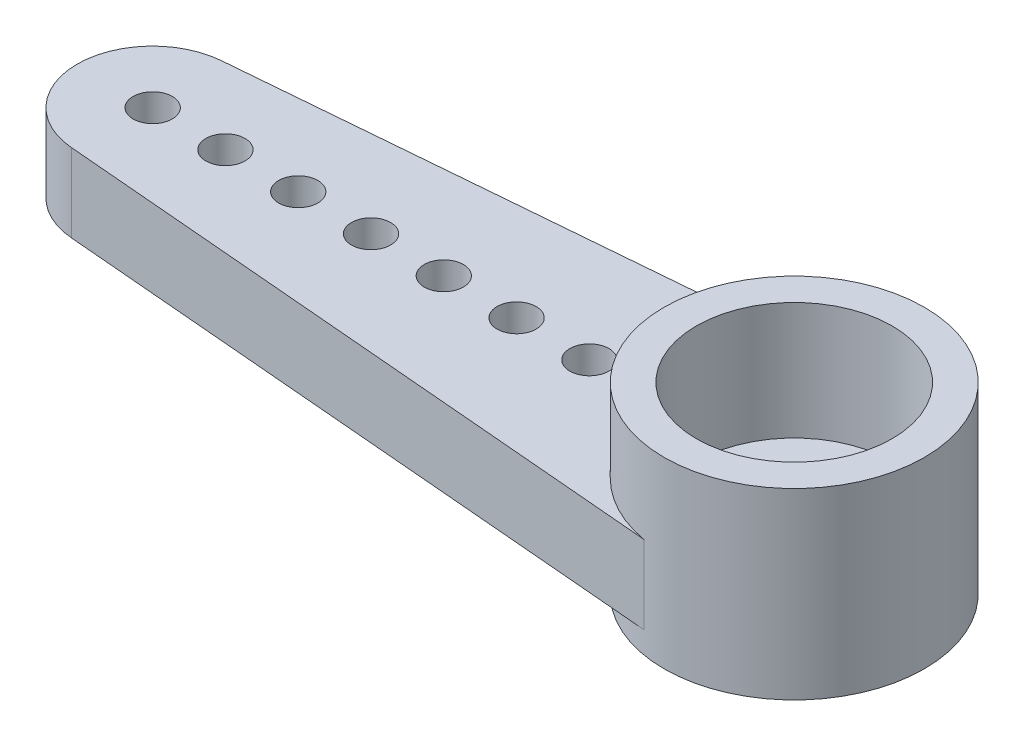
SolidWorks part; units mm, degrees
ref_plane "前视基准面" through (0, 0, 0) normal (0, 0, 1) x (1, 0, 0)
ref_plane "上视基准面" through (0, 0, 0) normal (0, 1, 0) x (1, 0, 0)
ref_plane "右视基准面" through (0, 0, 0) normal (1, 0, 0) x (0, 0, -1)
sketch "草图1" plane through (0, 0, 0) normal (0, 1, 0) x (1, 0, 0)
  circle A0 centre (0, 0) radius 3.325
  dimension "D1" = 6.65
extrude "凸台-拉伸1" add sketch "草图1" along normal mid plane 4.68
sketch "草图2" plane through (0, 2.34, 0) normal (0, 1, 0) x (1, 0, 0)
  circle A0 centre (0, 0) radius 2.5
  dimension "D1" = 5
extrude "切除-拉伸1" cut sketch "草图2" against normal blind 3 contours A0
sketch "草图3" plane through (0, -0.66, 0) normal (0, 1, 0) x (1, 0, 0)
  circle A0 centre (0, 0) radius 1
  dimension "D1" = 2
extrude "切除-拉伸2" cut sketch "草图3" against normal through all
ref_plane "基准面1" through (0, -2.39, 0) normal (0, 1, 0) x (1, 0, 0)
ref_plane "基准面2" through (0, 0.22, 0) normal (0, -1, 0) x (-1, 0, 0)
sketch "草图4" plane through (0, 0.22, 0) normal (0, -1, 0) x (-1, 0, 0)
  line L0 (0, 3.325) -> (0, -3.325) construction
  line L1 (-3.325, 0) -> (18.325, 0) construction
  line L2 (16.55, 1.92) -> (16.55, -1.92) construction
  line L3 (0, 3.325) -> (16.55, 1.92)
  line L4 (0, -3.325) -> (16.55, -1.92)
  circle A0 centre (0, 0) radius 3.325 construction
  arc A1 (16.55, 1.92) -> (16.55, -1.92) centre (16.3991, 0) cw
  arc A3 (0, 3.325) -> (0, -3.325) centre (-0.871, 0) cw
  point P9 (0, 0)
  point P13 (16.55, 0)
  point P17 (16.55, 0)
  dimension "D1" = 21.65
  dimension "D2" = 16.55
  dimension "D3" = 3.84
extrude "凸台-拉伸2" add sketch "草图4" along normal blind 2
sketch "草图5" plane through (0, -1.78, 0) normal (0, -1, 0) x (-1, 0, 0)
  line L0 (18.325, 0) -> (-49981.675, 0) construction
  arc A0 (16.55, -1.92) -> (16.55, 1.92) centre (16.3991, 0) ccw construction
  circle A3 centre (14.535, 0) radius 0.5
  circle A4 centre (0, 0) radius 1 construction
  circle A5 centre (16.395, 0) radius 0.5
  circle A7 centre (12.675, 0) radius 0.5
  circle A8 centre (10.815, 0) radius 0.5
  circle A9 centre (8.955, 0) radius 0.5
  circle A10 centre (7.095, 0) radius 0.5
  circle A11 centre (5.235, 0) radius 0.5
  circle A12 centre (0, 0) radius 3.325 construction
  point P5 (18.325, 0)
  point P7 (0, 0)
  point P9 (5.235, 0)
  point P10 (1, 0)
  point P17 (14.535, 0)
  point P18 (12.675, 0)
  point P19 (10.815, 0)
  point P20 (8.955, 0)
  point P29 (7.095, 0)
  point P31 (14.035, 0)
  point P32 (-3.325, 0)
  point P33 (0, 0)
  point P34 (0, 0)
  dimension "D2" = 1.86
  dimension "D5" = 1
  dimension "D6" = 1
  dimension "D7" = 1
  dimension "D11" = 1
  dimension "D13" = 1
  dimension "D14" = 1
  dimension "D15" = 1
  dimension "D4" = 1.86
  dimension "D8" = 1.86
  dimension "D9" = 1.86
  dimension "D10" = 1.86
  dimension "D12" = 1.86
  dimension "D16" = 17.36
extrude "切除-拉伸3" cut sketch "草图5" against normal blind 10
